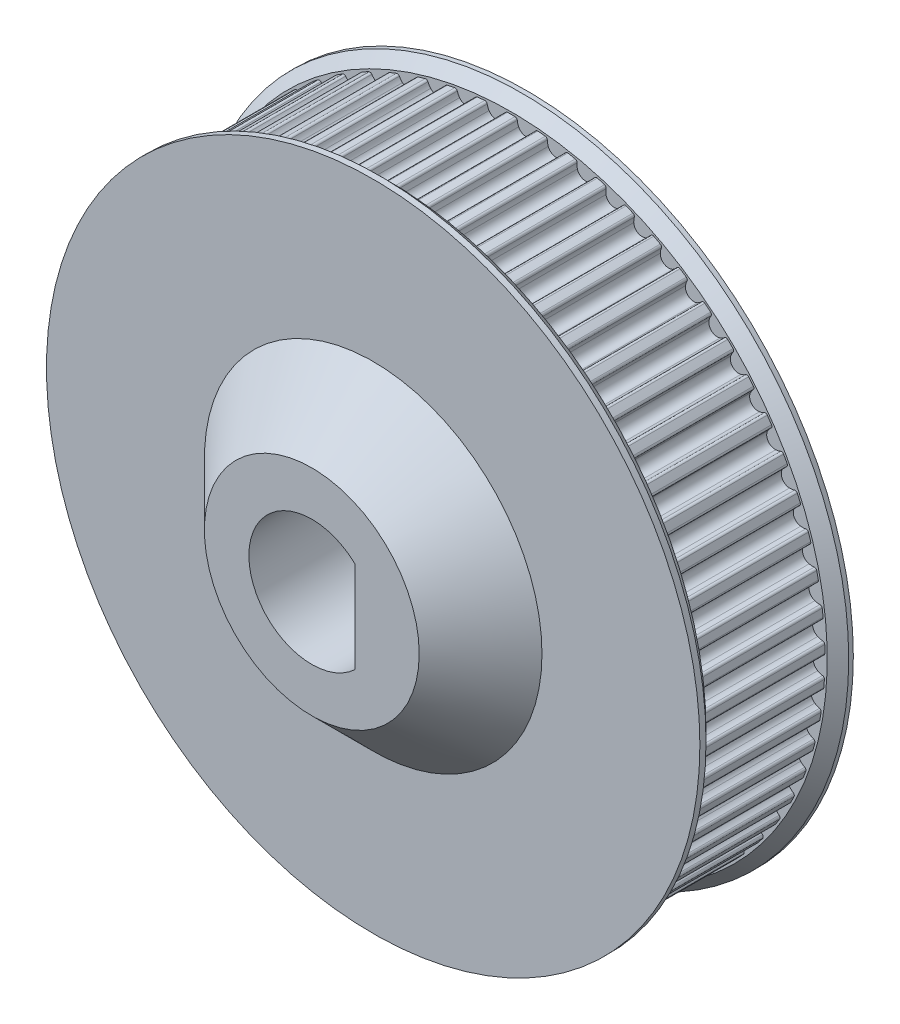
SolidWorks part; units mm, degrees
ref_plane "Front Plane" through (0, 0, 0) normal (0, 0, 1) x (1, 0, 0)
ref_plane "Top Plane" through (0, 0, 0) normal (0, 1, 0) x (1, 0, 0)
ref_plane "Right Plane" through (0, 0, 0) normal (1, 0, 0) x (0, 0, -1)
sketch "Sketch1" plane through (0, 0, 0) normal (0, 0, 1) x (1, 0, 0)
  circle A0 centre (0, 0) radius 20.6901
  dimension "D1" = 41.3803
extrude "Boss-Extrude1" add sketch "Sketch1" along normal mid plane 8
sketch "Sketch3" plane through (0, 0, 4) normal (0, 0, 1) x (1, 0, 0)
  line L0 (0, 0) -> (0, 20.6901) construction
  line L1 (0, 0) -> (0.9513, 19.6671) construction
  line L2 (0, 20.6901) -> (0, 20.4401)
  line L3 (1.3989, 20.6428) -> (1.3853, 20.4076) construction
  line L4 (0.9996, 20.666) -> (1.3989, 20.6428)
  line L5 (0.9513, 19.6671) -> (0.9996, 20.666) construction
  line L6 (1.9969, 20.5936) -> (1.9728, 20.3447)
  circle A0 centre (0, 0) radius 20.6901 construction
  arc A1 (0, 20.4401) -> (0.2432, 20.4387) centre (0, 0) cw
  circle A2 centre (0, 0) radius 20.6901
  circle A3 centre (0, 0) radius 20.6901
  arc A4 (0.2432, 20.4387) -> (0.3906, 20.3042) centre (0.2414, 20.2887) cw
  arc A5 (0.3906, 20.3042) -> (0.4799, 19.983) centre (1.3853, 20.4076) ccw
  arc A6 (0.4799, 19.983) -> (1.451, 19.936) centre (0.9779, 20.2165) ccw
  arc A7 (1.9728, 20.3447) -> (1.7305, 20.3668) centre (0, 0) ccw
  arc A8 (1.7305, 20.3668) -> (1.5708, 20.2471) centre (1.7178, 20.2173) ccw
  arc A9 (1.5708, 20.2471) -> (1.451, 19.936) centre (0.5908, 20.446) cw
  dimension "D4" = 0.15
  dimension "D5" = 1
  dimension "D7" = 0.55
  dimension "D1" = 2.769
  dimension "D3" = 0.25
  dimension "D6" = 0.4
  dimension "D8" = 1
  dimension "D2" = 0
extrude "Cut-Extrude1" cut sketch "Sketch3" against normal up to surface (8 mm away) contours A9 A8 A7 L6 L5 L4 L2 A1 A4 A5 A6 | L5 L4
pattern_circular "CirPattern1" count 65 over 360 about axis through (0, 0, 0) along (0, 0, 1) of "Cut-Extrude1"
sketch "Sketch4" plane through (0, 0, 4) normal (0, 0, 1) x (1, 0, 0)
  circle A0 centre (0, 0) radius 21.2901
  dimension "D1" = 42.5803
extrude "Boss-Extrude2" add sketch "Sketch4" along normal blind 1
mirror "Mirror1" about plane through (0, 0, 0) normal (0, 0, 1) of "Boss-Extrude2"
chamfer "Chamfer1" distance 0.7 angle 45 1 edges at (21.2901, 0, -4)
sketch "Sketch6" plane through (0, 0, 5) normal (0, 0, 1) x (1, 0, 0)
  circle A0 centre (0, 0) radius 7
  dimension "D1" = 14
extrude "Boss-Extrude3" add sketch "Sketch6" along normal blind 4
sketch "Sketch5" plane through (0, 0, 9) normal (0, 0, 1) x (1, 0, 0)
  circle A0 centre (0, 0) radius 4.1
  dimension "D1" = 8.2
extrude "Cut-Extrude2" cut sketch "Sketch5" against normal through all
sketch "Sketch7" plane through (0, 0, 9) normal (0, 0, 1) x (1, 0, 0)
  line L0 (2.8, 2.995) -> (2.8, -2.995)
  circle A0 centre (0, 0) radius 4.1 construction
  arc A1 (2.8, -2.995) -> (2.8, 2.995) centre (0, 0) ccw
  dimension "D1" = 2.8
extrude "Boss-Extrude4" add sketch "Sketch7" against normal up to surface (14 mm away) up to face at (4.1, 0, -5)
chamfer "Chamfer2" distance 4 angle 45 1 edges at (7, 0, 5)
chamfer "Chamfer3" distance 0.6 angle 45 1 edges at (21.2901, 0, 4)
equation "\"n\"= 65'teeth number"
equation "\"p\"= 2mm'tooth spacing"
equation "\"pd\"= \"n\" * \"p\" / pi"
equation "\"D1@Sketch1\"=\"pd\""
equation "\"halfToothAngle\"= 180 / \"n\""
equation "\"D1@Sketch3\"=\"halfToothAngle\""
equation "\"D1@CirPattern1\"=\"n\""
equation "\"flangeDia\"= \"pd\" + 1.2"
equation "\"D1@Sketch4\"=\"flangeDia\""
